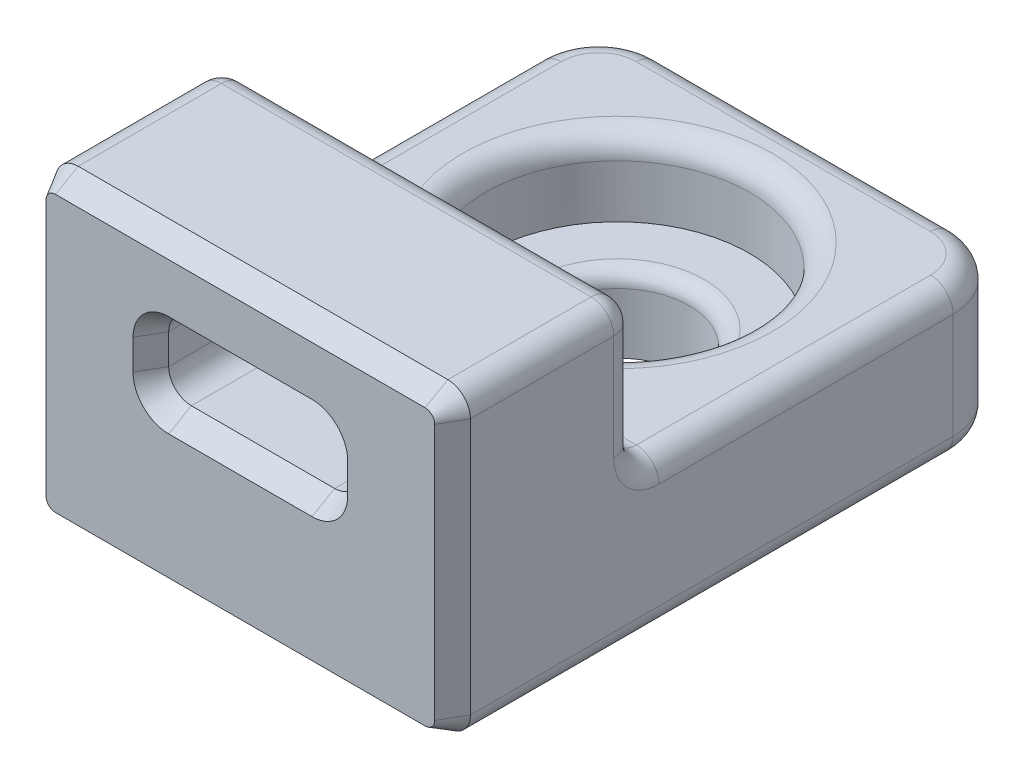
SolidWorks part; units mm, degrees
ref_plane "Front Plane" through (0, 0, 0) normal (0, 0, 1) x (1, 0, 0)
ref_plane "Top Plane" through (0, 0, 0) normal (0, 1, 0) x (1, 0, 0)
ref_plane "Right Plane" through (0, 0, 0) normal (1, 0, 0) x (0, 0, -1)
sketch "Sketch1" plane through (0, 0, 0) normal (0, 1, 0) x (1, 0, 0)
  line L1 (-6.985, -9.525) -> (6.985, -9.525)
  line L2 (-6.985, -9.525) -> (-6.985, 9.525)
  line L3 (-6.985, 9.525) -> (6.985, 9.525)
  line L4 (6.985, -9.525) -> (6.985, 9.525)
  line L5 (-6.985, -9.525) -> (6.985, 9.525) construction
  line L6 (-6.985, 9.525) -> (6.985, -9.525) construction
  circle A1 centre (0, 3.175) radius 2.413
  point P0 (0, 0)
  dimension "D3" = 6.35
  dimension "D4" = 4.826
  dimension "D1" = 19.05
  dimension "D2" = 13.97
extrude "Boss-Extrude1" add sketch "Sketch1" along normal blind 5.08
sketch "Sketch4" plane through (0, 0, 9.525) normal (0, 0, 1) x (1, 0, 0)
  line L1 (-6.985, 5.08) -> (-3.175, 5.08)
  line L2 (-6.985, 5.08) -> (-6.985, 7.62)
  line L3 (-6.985, 7.62) -> (-3.175, 7.62)
  line L4 (-3.175, 5.08) -> (-3.175, 7.62)
  line L5 (6.985, 5.08) -> (3.175, 5.08)
  line L6 (6.985, 5.08) -> (6.985, 7.62)
  line L7 (6.985, 7.62) -> (3.175, 7.62)
  line L8 (3.175, 5.08) -> (3.175, 7.62)
  line L9 (6.985, 7.62) -> (-6.985, 7.62)
  line L10 (6.985, 7.62) -> (6.985, 10.16)
  line L11 (6.985, 10.16) -> (-6.985, 10.16)
  line L12 (-6.985, 7.62) -> (-6.985, 10.16)
  line M15 (6.985, 5.08) -> (-6.985, 5.08)
  dimension "D1" = 6.35
  dimension "D2" = 2.54
  dimension "D3" = 2.54
extrude "Boss-Extrude4" add sketch "Sketch4" against normal blind 6.35 contours L12 L3 L9 L7 L10 L11 | L4 L3 L2 M15 | L8 L6 L7 M15 region at (-5.08, 6.35, 9.525) region at (0, 8.89, 9.525) region at (5.08, 6.35, 9.525)
sketch "Sketch5" plane through (0, 5.08, 0) normal (0, 1, 0) x (1, 0, 0)
  circle A0 centre (0, 3.175) radius 2.413 construction
  circle A1 centre (0, 3.175) radius 2.413 construction
  circle A2 centre (0, 3.175) radius 4.445
  dimension "D1" = 8.89
extrude "Cut-Extrude1" cut sketch "Sketch5" against normal blind 2.54
fillet "Fillet2" radius 0.762 21 edges at (3.175, 5.08, 6.35) (-3.175, 5.08, 6.35) (3.175, 7.62, 6.35) (-3.175, 7.62, 6.35) (-6.985, 10.16, 6.35) (6.985, 10.16, 6.35) (0, 10.16, 3.175) (5.08, 5.08, 3.175) (-5.08, 5.08, 3.175) (3.175, 6.35, 3.175) (0, 7.62, 3.175) (-3.175, 6.35, 3.175) (6.985, 5.08, -3.175) (-6.985, 5.08, -3.175) (6.985, 0, 0) (0, 0, -9.525) (-6.985, 0, 0) (0, 5.08, -9.525) (6.985, 7.62, 3.175) (-6.985, 7.62, 3.175) (0, 5.08, 1.27)
fillet "Fillet3" radius 2.032 6 edges at (6.985, 2.54, -9.525) (-6.985, 2.54, -9.525) (-6.7618, 0.2232, -9.3018) (-6.7618, 4.8568, -9.3018) (6.7618, 0.2232, -9.3018) (6.7618, 4.8568, -9.3018)
chamfer "Chamfer2" distance 0.762 angle 30 8 edges at (2.9518, 7.3968, 9.525) (0, 7.62, 9.525) (-2.9518, 7.3968, 9.525) (-3.175, 6.35, 9.525) (-2.9518, 5.3032, 9.525) (0, 5.08, 9.525) (2.9518, 5.3032, 9.525) (3.175, 6.35, 9.525) first distance on face at (2.8729, 7.3179, 6.731) first distance on face at (0, 7.62, 6.731) first distance on face at (-2.8729, 7.3179, 6.731) first distance on face at (-3.175, 6.35, 6.731) first distance on face at (-2.8729, 5.3821, 6.731) first distance on face at (0, 5.08, -8.382) first distance on face at (2.8729, 5.3821, 6.731) first distance on face at (3.175, 6.35, 6.731)
chamfer "Chamfer3" distance 0.762 angle 30 8 edges at (-6.985, 5.08, 9.525) (-6.7618, 9.9368, 9.525) (-6.7618, 0.2232, 9.525) (0, 10.16, 9.525) (0, 0, 9.525) (6.7618, 9.9368, 9.525) (6.7618, 0.2232, 9.525) (6.985, 5.08, 9.525) first distance on face at (-6.985, 4.9261, 2.0952) first distance on face at (-6.6829, 9.8579, 6.731) first distance on face at (-6.6829, 0.3021, 1.016) first distance on face at (0, 10.16, 6.731) first distance on face at (0, 0, -0.762) first distance on face at (6.6829, 9.8579, 6.731) first distance on face at (6.6829, 0.3021, 1.016) first distance on face at (6.985, 4.9261, 2.0952)
fillet "Fillet4" radius 0.508 1 edges at (0, 2.54, -0.762)
